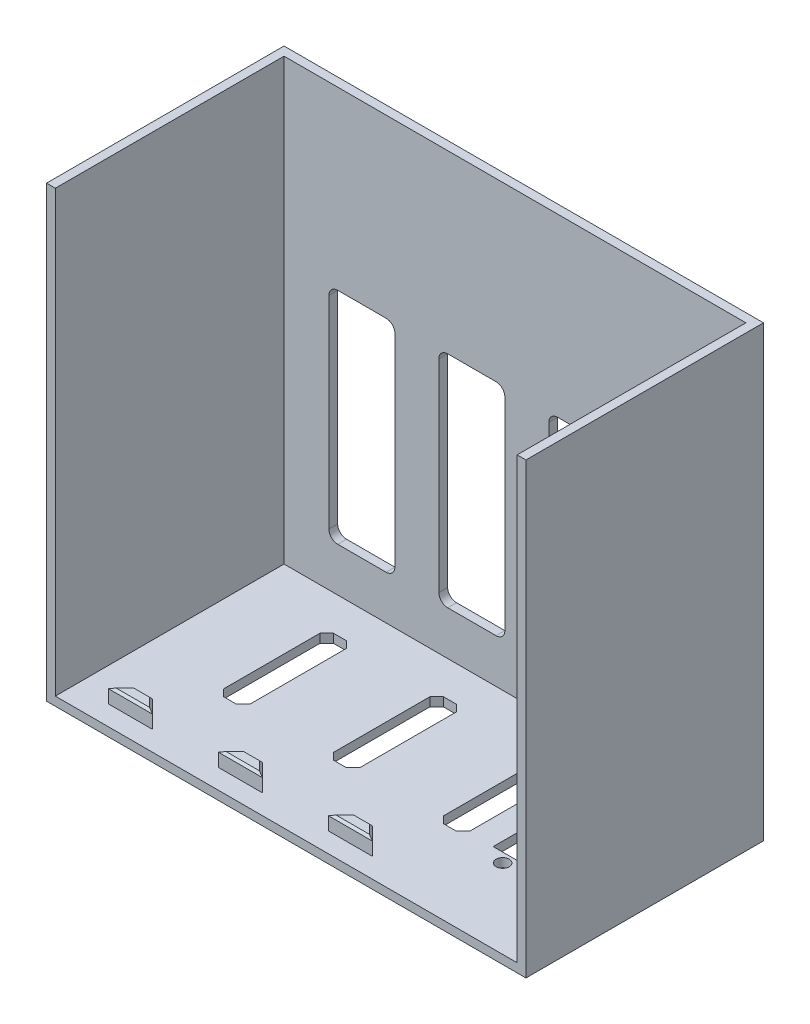
SolidWorks part; units mm, degrees
ref_plane "Front Plane" through (0, 0, 0) normal (0, 0, 1) x (1, 0, 0)
ref_plane "Top Plane" through (0, 0, 0) normal (0, 1, 0) x (1, 0, 0)
ref_plane "Right Plane" through (0, 0, 0) normal (1, 0, 0) x (0, 0, -1)
sketch "Sketch1" plane through (0, 0, 0) normal (1, 0, 0) x (0, 0, -1)
  line L0 (0, 0) -> (54, 0)
  line L1 (54, 0) -> (54, 102)
  line L2 (54, 102) -> (52, 102)
  line L3 (52, 102) -> (52, 2)
  line L4 (52, 2) -> (0, 2)
  line L5 (0, 2) -> (0, 0)
  dimension "D1" = 54
  dimension "D2" = 102
  dimension "D3" = 2
extrude "Boss-Extrude1" add sketch "Sketch1" along normal blind 105
sketch "Sketch3" plane through (105, 0, 0) normal (1, 0, 0) x (0, 0, -1)
  line L0 (0, 2) -> (0, 0) construction
  line L1 (54, 0) -> (0, 0)
  line L2 (54, 0) -> (54, 102)
  line L3 (54, 102) -> (0, 102)
  line L4 (0, 0) -> (0, 102)
  line L5 (54, 102) -> (52, 102) construction
extrude "Boss-Extrude2" add sketch "Sketch3" along normal blind 2
extrude "Boss-Extrude3" add sketch "Sketch3<2>" against normal blind 2 from surface starting at face at (0, 34.6667, -35.3333)
sketch "Sketch3<2>" plane through (105, 0, 0) normal (1, 0, 0) x (0, 0, -1) same geometry as "Sketch3"
sketch "Sketch4" plane through (0, 2, 0) normal (0, -1, 0) x (1, 0, 0)
  line L0 (42.6, -4.5) -> (39.6, -7.5)
  line L1 (32.6, -4.5) -> (42.6, -4.5)
  line L2 (35.6, -7.5) -> (32.6, -4.5)
  line L3 (17.6, -4.5) -> (14.6, -7.5)
  line L4 (7.6, -4.5) -> (17.6, -4.5)
  line L5 (10.6, -7.5) -> (7.6, -4.5)
  line L6 (14.6, -7.5) -> (10.6, -7.5)
  line L7 (39.6, -7.5) -> (35.6, -7.5)
  line L8 (67.6, -4.5) -> (64.6, -7.5)
  line L9 (57.6, -4.5) -> (67.6, -4.5)
  line L10 (60.6, -7.5) -> (57.6, -4.5)
  line L11 (64.6, -7.5) -> (60.6, -7.5)
  dimension "D1" = 3
extrude "Boss-Extrude4" add sketch "Sketch4" against normal blind 3.5
chamfer "Chamfer1" distance 0.5 angle 45 12 edges at (16.1, 5.5, -6) (12.6, 5.5, -7.5) (9.1, 5.5, -6) (12.6, 5.5, -4.5) (59.1, 5.5, -6) (62.6, 5.5, -7.5) (66.1, 5.5, -6) (62.6, 5.5, -4.5) (34.1, 5.5, -6) (37.6, 5.5, -7.5) (41.1, 5.5, -6) (37.6, 5.5, -4.5)
sketch "Sketch5" plane through (0, 0, -54) normal (0, 0, -1) x (-1, 0, 0)
  line L0 (-23.4115, 18.2) -> (-23.4115, 16.9) construction
  line L1 (-13.2, 19.3) -> (-13.2, 20.6) construction
  line L8 (-22.4115, 18.2) -> (-22.4115, 16.9) construction
  line L11 (-12.2, 19.3) -> (-12.2, 20.6) construction
  line L12 (-50.2, 62) -> (-50.2, 12)
  line L13 (-25.2, 62) -> (-10.2, 62)
  line L14 (-25.2, 62) -> (-25.2, 12)
  line L15 (-18.8115, 15.2) -> (-21.4286, 15.2) construction
  line L20 (-25.2, 12) -> (-10.2, 12)
  line L21 (-10.2, 62) -> (-10.2, 12)
  line L22 (-50.2, 62) -> (-35.2, 62)
  line L23 (-35.2, 62) -> (-35.2, 12)
  line L24 (-50.2, 12) -> (-35.2, 12)
  line L25 (-75.2, 62) -> (-75.2, 12)
  line L26 (-75.2, 62) -> (-60.2, 62)
  line L27 (-60.2, 62) -> (-60.2, 12)
  line L28 (-75.2, 12) -> (-60.2, 12)
  line L29 (2, 0) -> (2, 102) construction
  line L30 (-107, 0) -> (2, 0) construction
  dimension "D1" = 12.2
  dimension "D2" = 12
  dimension "D3" = 50
  dimension "D4" = 3
  dimension "D5" = 15
  dimension "D6" = 25
extrude "Cut-Extrude1" cut sketch "Sketch5" against normal through all
sketch "Sketch7" plane through (0, 0, 0) normal (0, -1, 0) x (1, 0, 0)
  line L0 (107, -54) -> (-2, -54) construction
  line L1 (17.7, -44) -> (23.7, -44)
  line L2 (17.7, -44) -> (17.7, -19)
  line L3 (17.7, -19) -> (23.7, -19)
  line L4 (-2, 0) -> (-2, -54) construction
  line L12 (23.7, -44) -> (23.7, -19)
  line L13 (42.7, -44) -> (42.7, -19)
  line L14 (42.7, -44) -> (48.7, -44)
  line L15 (48.7, -44) -> (48.7, -19)
  line L16 (42.7, -19) -> (48.7, -19)
  line L17 (67.7, -44) -> (67.7, -19)
  line L18 (67.7, -44) -> (73.7, -44)
  line L19 (73.7, -44) -> (73.7, -19)
  line L20 (67.7, -19) -> (73.7, -19)
  dimension "D2" = 19.7
  dimension "D3" = 25
  dimension "D4" = 6
  dimension "D6" = 25
  dimension "D1" = 10
  dimension "D5" = 3
extrude "Cut-Extrude2" cut sketch "Sketch7" against normal through all
fillet "Fillet1" radius 2 12 edges at (10.2, 62, -53) (10.2, 12, -53) (25.2, 12, -53) (25.2, 62, -53) (50.2, 62, -53) (50.2, 12, -53) (35.2, 12, -53) (35.2, 62, -53) (60.2, 62, -53) (60.2, 12, -53) (75.2, 12, -53) (75.2, 62, -53)
chamfer "Chamfer2" distance 1.5 angle 45 12 edges at (23.7, 1, -19) (17.7, 1, -19) (23.7, 1, -44) (17.7, 1, -44) (73.7, 1, -19) (67.7, 1, -19) (67.7, 1, -44) (73.7, 1, -44) (48.7, 1, -44) (42.7, 1, -44) (48.7, 1, -19) (42.7, 1, -19)
sketch "Sketch8" plane through (0, 0, 0) normal (0, -1, 0) x (-1, 0, 0)
  line L0 (2, 0) -> (2, 54) construction
  line L1 (-81.9, 36.35) -> (-85.5, 36.35)
  line L2 (-79.4, 33.85) -> (-79.4, 20.15)
  line L3 (-79.4, 20.15) -> (-88, 20.15)
  line L4 (-88, 33.85) -> (-88, 20.15)
  line L6 (-88, 27) -> (-107, 27) construction
  line L7 (-107, 0) -> (-107, 54) construction
  line L8 (-83.7, 18) -> (-83.7, 38.5) construction
  line L9 (-85.5, 36.35) -> (-85.5, 20.15) construction
  line L10 (-85.5, 28.25) -> (-83.7, 28.25) construction
  line L11 (-94.4, 21.85) -> (-101.6, 14.15) construction
  line L12 (-94.4, 21.85) -> (-101.6, 21.85)
  line L13 (-94.4, 21.85) -> (-94.4, 14.15)
  line L14 (-94.4, 14.15) -> (-101.6, 14.15)
  line L15 (-101.6, 21.85) -> (-101.6, 14.15)
  line L16 (-101.6, 30.65) -> (-94.4, 30.65)
  line L17 (-101.6, 30.65) -> (-101.6, 41.35)
  line L18 (-101.6, 41.35) -> (-94.4, 41.35)
  line L19 (-94.4, 30.65) -> (-94.4, 41.35)
  line L20 (-94.4, 14.15) -> (-101.6, 21.85) construction
  line L21 (-94.4, 30.65) -> (-101.6, 41.35) construction
  line L22 (-101.6, 30.65) -> (-94.4, 41.35) construction
  line L23 (-98, 0) -> (-98, 18) construction
  line L24 (-107, 0) -> (2, 0) construction
  line L25 (-98, 18) -> (-98, 36) construction
  line L26 (-98, 36) -> (-98, 54) construction
  line L27 (-107, 54) -> (2, 54) construction
  line L28 (-98, 18) -> (-98, 36) construction
  circle A0 centre (-83.7, 18) radius 1.5
  circle A1 centre (-83.7, 38.5) radius 1.5
  arc A2 (-88, 33.85) -> (-85.5, 36.35) centre (-85.5, 33.85) cw
  arc A3 (-81.9, 36.35) -> (-79.4, 33.85) centre (-81.9, 33.85) cw
  point P29 (-83.7, 36.35)
  point P39 (-98, 17.7652)
  point P40 (0, 0)
  dimension "D5" = 3
  dimension "D6" = 2.5
  dimension "D1" = 90
  dimension "D2" = 8.6
  dimension "D3" = 16.2
  dimension "D4" = 20.5
  dimension "D7" = 7.2
  dimension "D8" = 7.7
  dimension "D9" = 10.7
  dimension "D10" = 100
extrude "Cut-Extrude3" cut sketch "Sketch8" against normal through all
equation "\"D9@Sketch8\"=\"D8@Sketch8\"+3"
